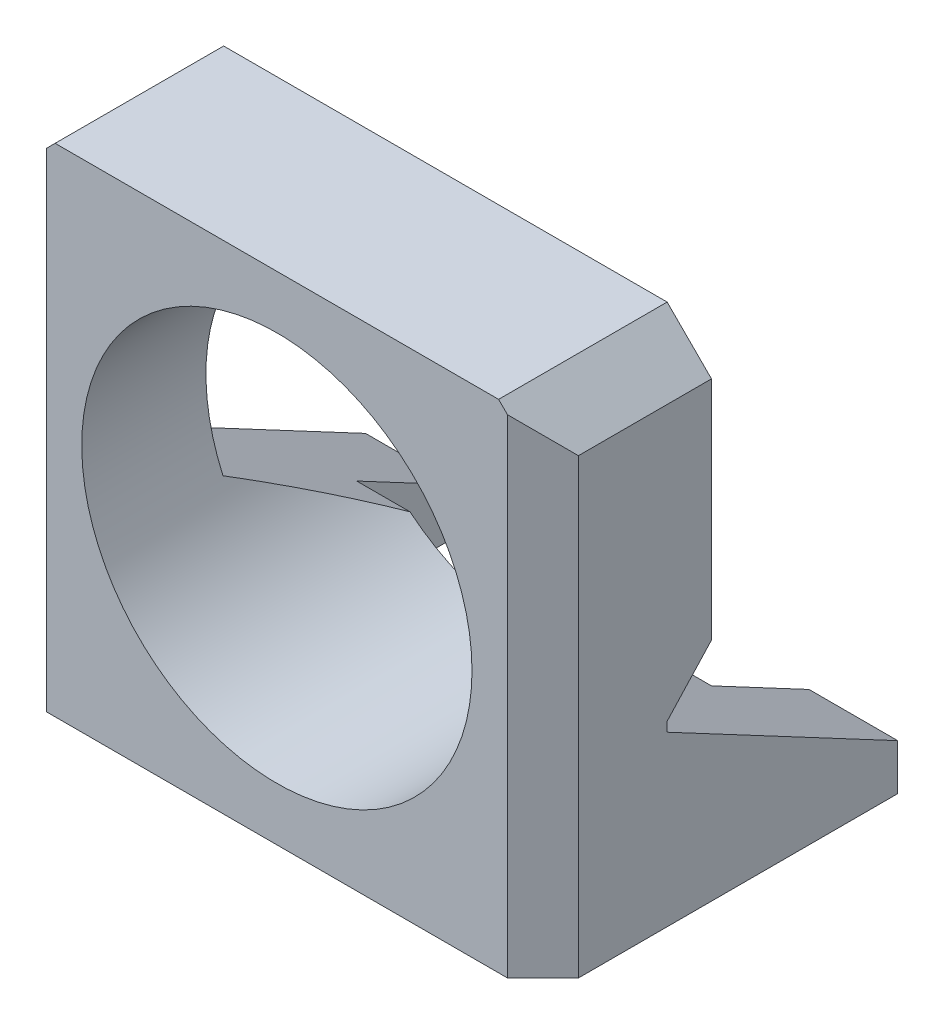
SolidWorks part; units mm, degrees
ref_plane "Front Plane" through (0, 0, 0) normal (0, 0, 1) x (1, 0, 0)
ref_plane "Top Plane" through (0, 0, 0) normal (0, 1, 0) x (1, 0, 0)
ref_plane "Right Plane" through (0, 0, 0) normal (1, 0, 0) x (0, 0, -1)
sketch "Sketch1" plane through (0, 0, 0) normal (0, 0, 1) x (1, 0, 0)
  line L0 (-15, 11.5) -> (-12.5, 14)
  line L1 (-12.5, 14) -> (12.5, 14)
  line L2 (-15, 11.5) -> (-15, -14)
  line L3 (-15, -14) -> (15, -14)
  line L4 (15, 11.5) -> (15, -14)
  line L5 (-15, 14) -> (15, -14) construction
  line L6 (-15, -14) -> (15, 14) construction
  line L7 (12.5, 14) -> (15, 11.5)
  circle A0 centre (0, 0) radius 11
  dimension "D1" = 22
  dimension "D2" = 30
  dimension "D3" = 28
extrude "Boss-Extrude1" add sketch "Sketch1" along normal blind 7
sketch "Sketch2" plane through (0, 0, 0) normal (0, 0, -1) x (-1, 0, 0)
  line L0 (0, 0) -> (0, -50000) construction
  line L1 (-15, -14) -> (-10, -14)
  line L2 (-15, -14) -> (-15, -11.5)
  line L3 (-15, -11.5) -> (-10, -11.5)
  line L4 (-10, -14) -> (-10, -11.5)
  line L5 (15, -11.5) -> (10, -11.5)
  line L6 (10, -14) -> (10, -11.5)
  line L7 (15, -14) -> (10, -14)
  line L8 (15, -14) -> (15, -11.5)
  dimension "D1" = 2.5
  dimension "D2" = 5
extrude "Boss-Extrude2" add sketch "Sketch2" along normal blind 13 contours L5 L6 L7 L8 | L2 L3 L4 L1
chamfer "Chamfer2" distance 2 angle 45 2 edges at (-10, -12.75, 0) (10, -12.75, 0)
sketch "Sketch5" plane through (0, -14, 0) normal (0, -1, 0) x (1, 0, 0)
  line L0 (-10, -7.5) -> (10, -7.5)
  line L1 (-10, -13) -> (-10, -2) construction
  line L2 (10, -13) -> (10, -2) construction
  line L3 (10, -7.5) -> (10, -2)
  line L4 (10, -2) -> (8, 0)
  line L5 (8, 0) -> (-8, 0)
  line L6 (-8, 0) -> (-10, -2)
  line L7 (-10, -2) -> (-10, -7.5)
  line M5 (-10, -13) -> (-10, -2)
  line M6 (-10, -2) -> (-8, 0)
  line M7 (-8, 0) -> (8, 0)
  line M8 (8, 0) -> (10, -2)
  line M9 (10, -2) -> (10, -13)
extrude "Boss-Extrude6" add sketch "Sketch5" against normal up to surface (2.5 mm away) contours L0 M5 M9 M8 M7 M6 region at (0, -14, -3.8345) up to face at (11.6, -11.5, -5.6)
chamfer "Chamfer3" distance 2 angle 45 1 edges at (15, -1.25, 7)
chamfer "Chamfer4" distance 2 angle 45 1 edges at (-15, -1.25, 7)
sketch "Sketch4" plane through (0, 0, 0) normal (0, 0, -1) x (-1, 0, 0)
  line L8 (0, 0) -> (0, 50000) construction
  line L14 (-15, -1.25) -> (15, 11.5)
  line L15 (15, 11.5) -> (12.5, 14)
  line L16 (12.5, 14) -> (-12.5, 14)
  line L17 (-12.5, 14) -> (-15, 11.5)
  line L18 (-15, 11.5) -> (-15, -1.25)
  line L19 (-15, 11.5) -> (-15, -14) construction
  point P8 (-15, -1.25)
extrude "Boss-Extrude4" add sketch "Sketch4" along normal blind 2.5
chamfer "Chamfer6" distance 2.5 2 edges at (12.9953, -0.398, 0) (-11.1504, 9.8639, 0)
chamfer "Chamfer7" distance 7 angle 62 1 edges at (0, -11.5, 0) first distance on face at (-0.5726, -4.3777, 0)
sketch "Sketch6" plane through (0, -14, 0) normal (0, -1, 0) x (1, 0, 0)
  line L0 (-15, 5) -> (-15, -13) construction
  line L1 (-7.55, 0.5081) -> (-7.55, 4.4919)
  line L2 (-7.55, 4.4919) -> (-11, 6.4837)
  line L3 (-11, 6.4837) -> (-14.45, 4.4919)
  line L4 (-14.45, 4.4919) -> (-14.45, 0.5081)
  line L5 (-14.45, 0.5081) -> (-11, -1.4837)
  line L6 (-11, -1.4837) -> (-7.55, 0.5081)
  line L7 (0, 0) -> (0, 50000) construction
  line L8 (11, -1.4837) -> (7.55, 0.5081)
  line L9 (14.45, 0.5081) -> (11, -1.4837)
  line L10 (14.45, 4.4919) -> (14.45, 0.5081)
  line L11 (11, 6.4837) -> (14.45, 4.4919)
  line L12 (7.55, 4.4919) -> (11, 6.4837)
  line L13 (7.55, 0.5081) -> (7.55, 4.4919)
  circle A0 centre (-11, 2.5) radius 2 construction
  circle A1 centre (-11, 2.5) radius 2
  circle A2 centre (-11, 2.5) radius 3.45 construction
  point P21 (-11, 2.5)
  dimension "D1" = 6.9
extrude "Cut-Extrude1" cut sketch "Sketch6" against normal blind 2.5 from offset 3 offset against normal yes
sketch "Sketch7" plane through (0, -14, 0) normal (0, -1, 0) x (1, 0, 0)
  circle A0 centre (11, 2.5) radius 2 construction
  circle A1 centre (-11, 2.5) radius 2 construction
  circle A2 centre (11, 2.5) radius 2
  circle A3 centre (-11, 2.5) radius 2
extrude "Cut-Extrude2" cut sketch "Sketch7" against normal blind 6
